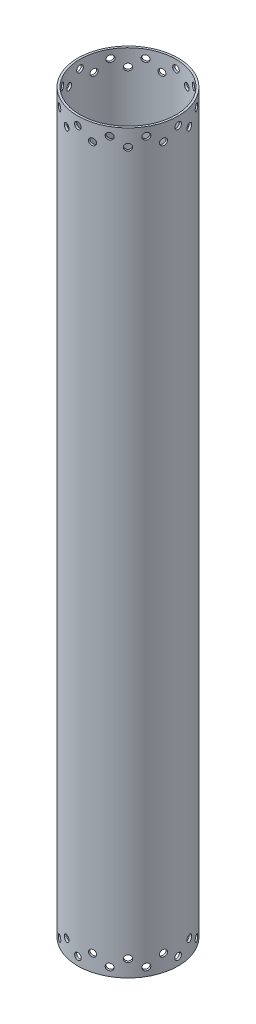
SolidWorks part; units mm, degrees
material "6061-T6 (SS)"
ref_plane "Front Plane" through (0, 0, 0) normal (0, 0, 1) x (1, 0, 0)
ref_plane "Top Plane" through (0, 0, 0) normal (0, 1, 0) x (1, 0, 0)
ref_plane "Right Plane" through (0, 0, 0) normal (1, 0, 0) x (0, 0, -1)
sketch "Sketch2" plane through (0, 0, 0) normal (0, 1, 0) x (1, 0, 0)
  circle A0 centre (0, 0) radius 76.2
  circle A1 centre (0, 0) radius 73.025
  dimension "D1" = 152.4
  dimension "D2" = 3.175
extrude "Boss-Extrude1" add sketch "Sketch2" along normal blind 1117.6
sketch "Sketch3" plane through (0, 0, 0) normal (0, 0, 1) x (1, 0, 0)
  line L0 (0, 1117.6) -> (0, 1104.9) construction
  line L1 (73.025, 1117.6) -> (-73.025, 1117.6) construction
  circle A0 centre (0, 1104.9) radius 5.0419
  dimension "D1" = 10.0838
  dimension "D2" = 12.7
extrude "Cut-Extrude1" cut sketch "Sketch3" against normal blind 1143
ref_plane "Plane1" through (-19.722, 0, 73.6035) normal (-0.2588, 0, 0.9659) x (0, -1, 0)
sketch "Sketch6" plane through (-19.722, 0, 73.6035) normal (-0.2588, 0, 0.9659) x (0, -1, 0)
  line L0 (-1117.6, 0) -> (-1092.2, 0) construction
  line L1 (-1117.6, 76.2) -> (-1117.6, -76.2) construction
  circle A0 centre (-1092.2, 0) radius 5.0419
  dimension "D1" = 10.0838
extrude "Cut-Extrude2" cut sketch "Sketch6" against normal blind 25.4
pattern_circular "CirPattern2" count 12 over 360 about axis through (0, 1117.6, 0) along (0, -1, 0) of "Cut-Extrude2", "Cut-Extrude1"
ref_plane "Plane2" through (0, 558.8, 0) normal (0, 1, 0) x (1, 0, 0)
mirror "Mirror1" about plane through (0, 558.8, 0) normal (0, 1, 0) of "CirPattern2"
equation "\"holeDia\"=0.397"
equation "\"D1@Sketch3\"=\"holeDia\""
equation "\"D1@Sketch6\"=\"holeDia\""
equation "\"numHoles\"=12"
equation "\"D1@CirPattern2\"=\"numHoles\""
equation "\"D1@Plane1\"=180/\"numHoles\""
